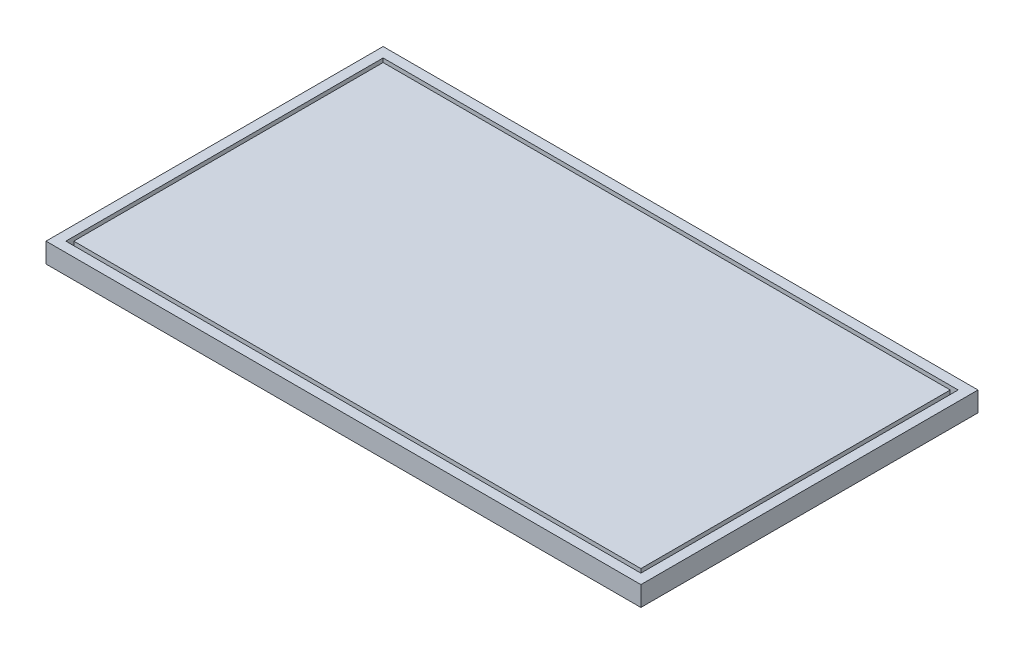
SolidWorks part; units mm, degrees
ref_plane "Front Plane" through (0, 0, 0) normal (0, 0, 1) x (1, 0, 0)
ref_plane "Top Plane" through (0, 0, 0) normal (0, 1, 0) x (1, 0, 0)
ref_plane "Right Plane" through (0, 0, 0) normal (1, 0, 0) x (0, 0, -1)
sketch "Sketch1" plane through (0, 0, 0) normal (0, 1, 0) x (1, 0, 0)
  line L1 (-160.5753, 72.0127) -> (139.4247, 72.0127)
  line L2 (-160.5753, 72.0127) -> (-160.5753, -97.9873)
  line L3 (-160.5753, -97.9873) -> (139.4247, -97.9873)
  line L4 (139.4247, 72.0127) -> (139.4247, -97.9873)
  dimension "D1" = 170
  dimension "D2" = 300
extrude "Boss-Extrude1" add sketch "Sketch1" along normal blind 10
sketch "Sketch2" plane through (0, 10, 0) normal (0, 1, 0) x (1, 0, 0)
  line L0 (139.4247, 72.0127) -> (-160.5753, 72.0127) construction
  line L1 (-155.5753, 67.0127) -> (134.4247, 67.0127)
  line L2 (-155.5753, 67.0127) -> (-155.5753, -92.9873)
  line L3 (-155.5753, -92.9873) -> (134.4247, -92.9873)
  line L4 (134.4247, 67.0127) -> (134.4247, -92.9873)
  line L5 (-153.5753, 65.0127) -> (132.4247, 65.0127)
  line L6 (-153.5753, 65.0127) -> (-153.5753, -90.9873)
  line L7 (-153.5753, -90.9873) -> (132.4247, -90.9873)
  line L8 (132.4247, 65.0127) -> (132.4247, -90.9873)
  line L9 (-160.5753, -97.9873) -> (139.4247, -97.9873) construction
  line L10 (-160.5753, 72.0127) -> (-160.5753, -97.9873) construction
  line L11 (139.4247, -97.9873) -> (139.4247, 72.0127) construction
  dimension "D1" = 5
  dimension "D2" = 5
  dimension "D3" = 5
  dimension "D4" = 5
  dimension "D5" = 2
  dimension "D6" = 2
  dimension "D7" = 2
  dimension "D8" = 2
extrude "Cut-Extrude1" cut sketch "Sketch2" against normal blind 5
sketch "Sketch3" plane through (0, 0, 0) normal (0, 1, 0) x (1, 0, 0)
  line L0 (-10.5753, -932.9873) -> (-10.5753, 49067.0127) construction
  line L1 (134.4247, 67.0127) -> (-155.5753, 67.0127) construction
  line L3 (-151.2048, 62.5) -> (45.2452, 62.5)
  line L4 (-151.2048, 62.5) -> (-151.2048, -89.2)
  line L5 (-151.2048, -89.2) -> (45.2452, -89.2)
  line L6 (45.2452, 62.5) -> (45.2452, -89.2)
  point P5 (-10.5753, 67.0127)
  dimension "D1" = 196.45
  dimension "D2" = 151.7
